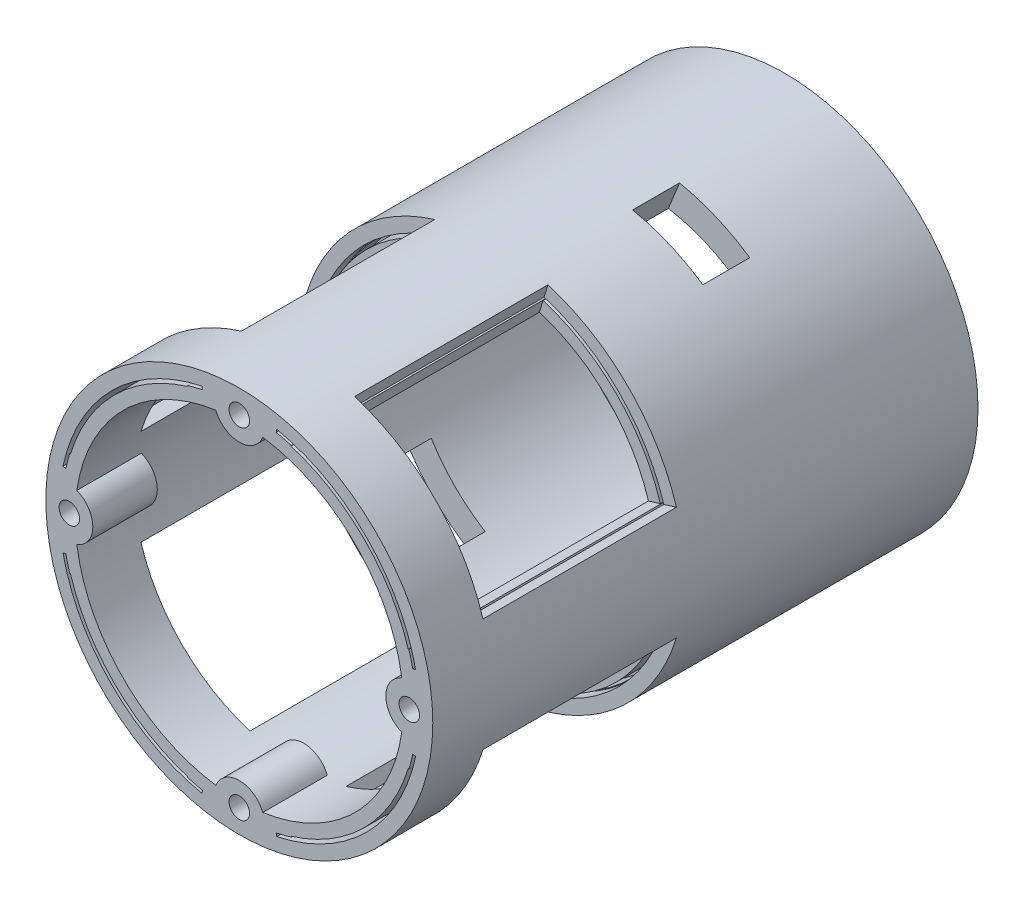
SolidWorks part; units mm, degrees
material "PEI"
ref_plane "Alzado" through (0, 0, 0) normal (0, 0, 1) x (1, 0, 0)
ref_plane "Planta" through (0, 0, 0) normal (0, 1, 0) x (1, 0, 0)
ref_plane "Vista lateral" through (0, 0, 0) normal (1, 0, 0) x (0, 0, -1)
sketch "Croquis1" plane through (0, 0, 0) normal (0, 0, 1) x (1, 0, 0)
  circle A0 centre (0, 0) radius 33
  circle A1 centre (0, 0) radius 28
  dimension "D1" = 66
  dimension "D2" = 5
extrude "Boss-Extrude1" add sketch "Croquis1" along normal blind 93
sketch "Croquis2" plane through (0, 0, 93) normal (0, 0, 1) x (1, 0, 0)
  line L0 (0, 0) -> (-6.3933, -30.078) construction
  line L1 (0, 0) -> (-30.078, -6.3933) construction
  line L2 (0, 0) -> (0, -30.5) construction
  line L3 (0, 0) -> (-30.5, 0) construction
  line L4 (-30.078, -6.3933) -> (-29.589, -6.2893)
  line L5 (-6.3933, -30.078) -> (-6.2893, -29.589)
  line L6 (-30.078, 6.3933) -> (-29.589, 6.2893)
  line L7 (-6.3933, 30.078) -> (-6.2893, 29.589)
  line L8 (6.3933, 30.078) -> (6.2893, 29.589)
  line L9 (30.078, 6.3933) -> (29.589, 6.2893)
  line L10 (30.078, -6.3933) -> (29.589, -6.2893)
  line L11 (6.3933, -30.078) -> (6.2893, -29.589)
  circle A0 centre (0, 0) radius 30.25 construction
  circle A1 centre (0, 0) radius 30.75 construction
  circle A2 centre (0, 0) radius 33 construction
  circle A3 centre (0, 0) radius 30.5 construction
  arc A4 (-6.3933, -30.078) -> (-30.078, -6.3933) centre (0, 0) cw
  arc A5 (-6.2893, -29.589) -> (-29.589, -6.2893) centre (0, 0) cw
  arc A6 (-30.078, 6.3933) -> (-6.3933, 30.078) centre (0, 0) cw
  arc A7 (-29.589, 6.2893) -> (-6.2893, 29.589) centre (0, 0) cw
  arc A8 (6.3933, 30.078) -> (30.078, 6.3933) centre (0, 0) cw
  arc A9 (6.2893, 29.589) -> (29.589, 6.2893) centre (0, 0) cw
  arc A10 (30.078, -6.3933) -> (6.3933, -30.078) centre (0, 0) cw
  arc A11 (29.589, -6.2893) -> (6.2893, -29.589) centre (0, 0) cw
  circle A12 centre (0, 0) radius 28 construction
  point P4 (-6.3413, -29.8335)
  point P32 (0, 0)
  dimension "D3" = 12
  dimension "D4" = 12
  dimension "D1" = 0.5
  dimension "D2" = 5
  dimension "D6" = 2.5
  dimension "D5" = 4
extrude "Cortar-Extruir1" cut sketch "Croquis2" against normal blind 45
ref_axis "Eje1" through (0, 0, 93) along (0, 0, -1)
ref_plane "Plano2" through (0, 0, 0) normal (0.9563, -0.2924, 0) x (0, 0, -1)
sketch "Croquis4" plane through (0, 0, 0) normal (0.9563, -0.2924, 0) x (0, 0, -1)
  line L0 (-83, 33) -> (-83, 30.6339)
  line L1 (0, 33) -> (-93, 33) construction
  line L2 (-83, 27.7679) -> (-50, 27.7679)
  line L3 (-50, 27.7679) -> (-50, 30.1339)
  line L4 (-50, 33) -> (-83, 33)
  line L5 (-97, 29) -> (-42, 29) construction
  line L6 (-93, 33) -> (-93, -33) construction
  line L7 (-93, 30.6339) -> (-83, 30.6339)
  line L8 (-45, 30.6339) -> (-45, 30.1339)
  line L9 (-45, 30.1339) -> (-50, 30.1339)
  line L10 (-93, 30.1339) -> (-93, 30.6339)
  line L11 (-83, 30.1339) -> (-93, 30.1339)
  line L12 (-83, 30.1339) -> (-83, 27.7679)
  line L13 (-50, 30.6339) -> (-45, 30.6339)
  line L14 (-50, 30.6339) -> (-50, 33)
  line L15 (-93, 30.633) -> (-93, 30.1349) construction
  point P20 (-93, 30.3839)
  point P21 (-93, 30.3839)
  dimension "D2" = 43
  dimension "D3" = 0.5
  dimension "D5" = 5
  dimension "D6" = 10
revolve "Cortar-Revolución2" cut sketch "Croquis4" angle 56 about axis through (0, 0, 93) along (0, 0, -1)
pattern_circular "MatrizC2" count 4 over 360 about axis through (0, 0, 93) along (0, 0, -1) of "Cortar-Revolución2"
sketch "Sketch8" plane through (0, 0, 0) normal (0, 0, -1) x (-1, 0, 0)
  arc A0 (-4, -27.7128) -> (4, -27.7128) centre (0, 0) ccw
  circle A1 centre (0, 0) radius 28 construction
  arc A2 (-4, -27.7128) -> (4, -27.7128) centre (0, -29.2908) cw
  arc A3 (-27.7128, 4) -> (-27.7128, -4) centre (0, 0) ccw
  arc A4 (-27.7128, 4) -> (-27.7128, -4) centre (-29.2908, 0) cw
  arc A5 (4, 27.7128) -> (-4, 27.7128) centre (0, 0) ccw
  arc A6 (4, 27.7128) -> (-4, 27.7128) centre (0, 29.2908) cw
  arc A7 (27.7128, -4) -> (27.7128, 4) centre (0, 0) ccw
  arc A8 (27.7128, -4) -> (27.7128, 4) centre (29.2908, 0) cw
  point P8 (0, -24.9908)
  point P20 (0, 0)
  dimension "D1" = 4.3
  dimension "D2" = 8
  dimension "D3" = 4
extrude "Boss-Extrude4" add sketch "Sketch8" against normal blind 11
sketch "Sketch9" plane through (0, 0, 0) normal (0, 0, -1) x (-1, 0, 0)
  circle A0 centre (0, -29) radius 1.75
  circle A1 centre (0, 0) radius 29 construction
  circle A2 centre (0, 0) radius 33 construction
  circle A3 centre (-29, 0) radius 1.75
  circle A4 centre (0, 29) radius 1.75
  circle A5 centre (29, 0) radius 1.75
  point P16 (0, 0)
  dimension "D1" = 4
  dimension "D2" = 3.5
  dimension "D3" = 4
extrude "Cut-Extrude3" cut sketch "Sketch9" against normal blind 10
ref_plane "Mid plane" through (0, 0, 46.5) normal (0, 0, 1) x (1, 0, 0)
mirror "Mirror1" about plane through (0, 0, 46.5) normal (0, 0, 1) of "Cut-Extrude3", "Boss-Extrude4"
ref_plane "Plano para USB y Switch" through (-23.3345, -23.3345, 0) normal (-0.7071, -0.7071, 0) x (0, 0, -1)
sketch "Sketch10" plane through (-23.3345, -23.3345, 0) normal (-0.7071, -0.7071, 0) x (0, 0, -1)
  line L0 (0, -33) -> (0, 33) construction
  line L1 (-10.5, 7.5) -> (-3.5, 7.5)
  line L2 (-10.5, 7.5) -> (-10.5, -7.5)
  line L3 (-10.5, -7.5) -> (-3.5, -7.5)
  line L4 (-3.5, 7.5) -> (-3.5, -7.5)
  line L5 (-10.5, 7.5) -> (-3.5, -7.5) construction
  line L6 (-10.5, -7.5) -> (-3.5, 7.5) construction
  line L8 (-44.4, 6.5) -> (-36.4, 6.5)
  line L9 (-44.4, 6.5) -> (-44.4, -6.5)
  line L10 (-44.4, -6.5) -> (-36.4, -6.5)
  line L11 (-36.4, 6.5) -> (-36.4, -6.5)
  line L12 (-44.4, 6.5) -> (-36.4, -6.5) construction
  line L13 (-44.4, -6.5) -> (-36.4, 6.5) construction
  point P0 (-7, 0)
  point P7 (0, 0)
  point P9 (-40.4, 0)
  dimension "D1" = 7
  dimension "D2" = 15
  dimension "D3" = 7
  dimension "D4" = 13
  dimension "D5" = 8
  dimension "D6" = 40.4
extrude "Corte USB y Switch" cut sketch "Sketch10" against normal blind 10
ref_plane "Plano USB PCB_C" through (12.362, 30.5971, 0) normal (0.3746, 0.9272, 0) x (0, 0, -1)
sketch "Sketch11" plane through (12.362, 30.5971, 0) normal (0.3746, 0.9272, 0) x (0, 0, -1)
  line L0 (0, -33) -> (0, 33) construction
  line L1 (-32.5, 6) -> (-24.5, 6)
  line L2 (-32.5, 6) -> (-32.5, -7)
  line L3 (-32.5, -7) -> (-24.5, -7)
  line L4 (-24.5, 6) -> (-24.5, -7)
  line L5 (-32.5, 6) -> (-24.5, -7) construction
  line L6 (-32.5, -7) -> (-24.5, 6) construction
  point P0 (-28.5, -0.5)
  point P8 (-26, -1.6868)
  dimension "D1" = 0.5
  dimension "D2" = 8
  dimension "D3" = 13
  dimension "D4" = 24.5
extrude "Cut-Extrude5" cut sketch "Sketch11" against normal blind 10
equation "\"D6@Croquis2\"=\"D2@Croquis2\"/2"
